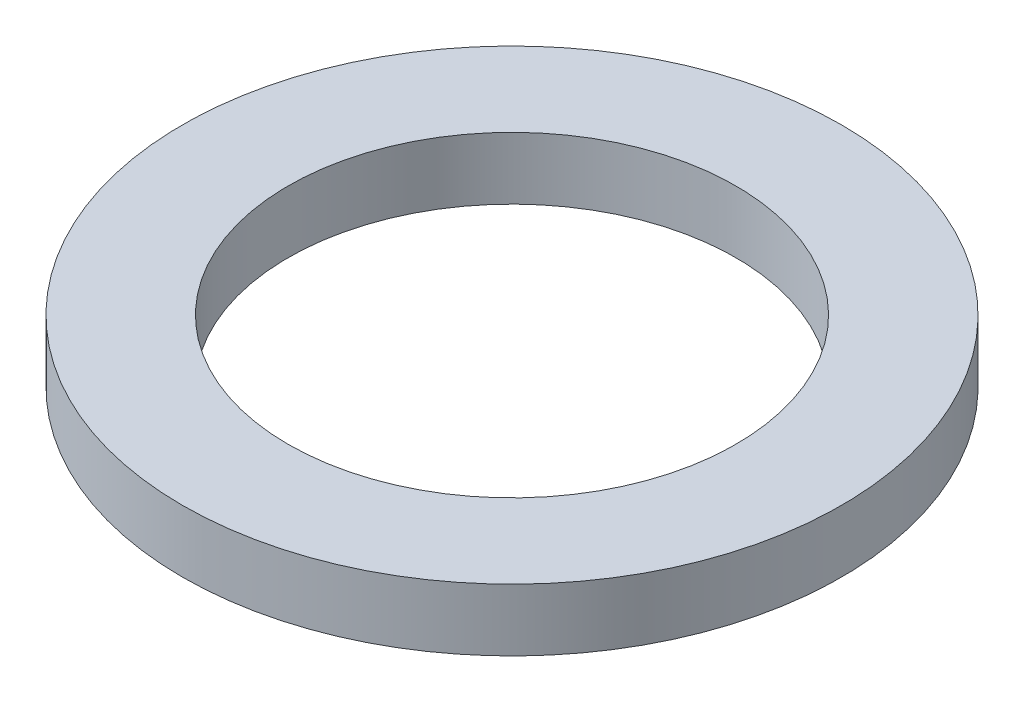
SolidWorks part; units mm, degrees
ref_plane "Front Plane" through (0, 0, 0) normal (0, 0, 1) x (1, 0, 0)
ref_plane "Top Plane" through (0, 0, 0) normal (0, 1, 0) x (1, 0, 0)
ref_plane "Right Plane" through (0, 0, 0) normal (1, 0, 0) x (0, 0, -1)
sketch "Sketch1" plane through (0, 0, 0) normal (0, 1, 0) x (1, 0, 0)
  circle A0 centre (0, 0) radius 6.731
  circle A1 centre (0, 0) radius 4.572
  dimension "D1" = 13.462
  dimension "D2" = 9.144
extrude "Boss-Extrude1" add sketch "Sketch1" along normal blind 1.27
